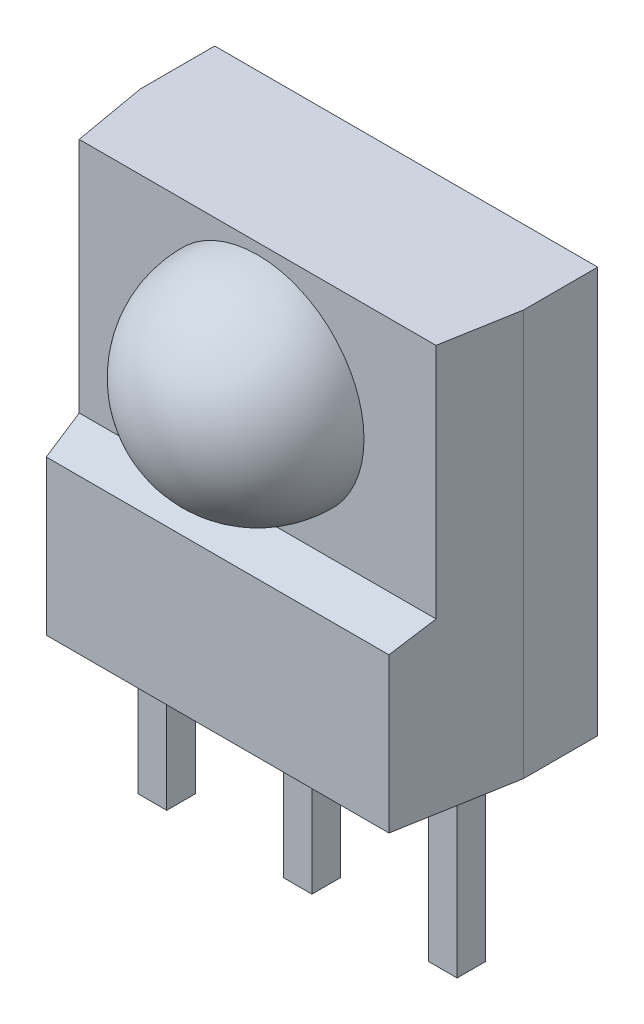
SolidWorks part; units mm, degrees
ref_plane "Plano frontal" through (0, 0, 0) normal (0, 0, 1) x (1, 0, 0)
ref_plane "Plano superior" through (0, 0, 0) normal (0, 1, 0) x (1, 0, 0)
ref_plane "Plano direito" through (0, 0, 0) normal (1, 0, 0) x (0, 0, -1)
sketch "Esboço1" plane through (0, 0, 0) normal (0, 1, 0) x (1, 0, 0)
  line L1 (-3.35, -1.65) -> (3.35, -1.65)
  line L2 (-3.35, -1.65) -> (-3.35, 1.65)
  line L3 (-3.35, 1.65) -> (3.35, 1.65)
  line L4 (3.35, -1.65) -> (3.35, 1.65)
  line L5 (-3.35, -1.65) -> (3.35, 1.65) construction
  line L6 (-3.35, 1.65) -> (3.35, -1.65) construction
  point P0 (0, 0)
  dimension "D1" = 6.7
  dimension "D2" = 3.3
extrude "Ressalto-extrusão1" add sketch "Esboço1" along normal blind 7.1
sketch "Esboço2" plane through (0, 0, 1.65) normal (0, 0, 1) x (1, 0, 0)
  line L0 (3.35, 7.1) -> (3.35, 0) construction
  line L1 (-3.35, 7.1) -> (3.35, 7.1)
  line L2 (-3.35, 7.1) -> (-3.35, 3)
  line L3 (-3.35, 3) -> (3.35, 3)
  line L4 (3.35, 7.1) -> (3.35, 3)
  line L5 (-3.35, 0) -> (3.35, 0) construction
  dimension "D1" = 3
extrude "Corte-extrusão1" cut sketch "Esboço2" against normal blind 0.7
sketch "Esboço3" plane through (0, 0, 0.95) normal (0, 0, 1) x (1, 0, 0)
  line L0 (0, 7.1) -> (0, 3) construction
  line L1 (3.35, 7.1) -> (-3.35, 7.1) construction
  line L2 (-3.35, 3) -> (3.35, 3) construction
  line L3 (0, 6.911) -> (0, 3.189)
  arc A0 (0, 3.189) -> (0, 6.911) centre (0, 5.05) ccw
revolve "Revolução1" add sketch "Esboço3" angle 180 about L0
sketch "Esboço4" plane through (0, 0, 0) normal (0, -1, 0) x (1, 0, 0)
  line L0 (-3.35, 0) -> (3.35, 0) construction
  line L1 (-3.35, -1.65) -> (-3.35, 1.65) construction
  line L2 (3.35, 1.65) -> (3.35, -1.65) construction
  line L3 (-0.25, -0.25) -> (0.25, -0.25)
  line L4 (-2.79, -0.25) -> (-2.29, -0.25)
  line L5 (-2.79, -0.25) -> (-2.79, 0.25)
  line L6 (-2.79, 0.25) -> (-2.29, 0.25)
  line L7 (-2.29, -0.25) -> (-2.29, 0.25)
  line L8 (-2.79, -0.25) -> (-2.29, 0.25) construction
  line L9 (-2.79, 0.25) -> (-2.29, -0.25) construction
  line L10 (-0.25, -0.25) -> (-0.25, 0.25)
  line L11 (-0.25, 0.25) -> (0.25, 0.25)
  line L12 (0.25, -0.25) -> (0.25, 0.25)
  line L13 (-0.25, -0.25) -> (0.25, 0.25) construction
  line L14 (-0.25, 0.25) -> (0.25, -0.25) construction
  line L15 (2.29, -0.25) -> (2.79, -0.25)
  line L16 (2.29, -0.25) -> (2.29, 0.25)
  line L17 (2.29, 0.25) -> (2.79, 0.25)
  line L18 (2.79, -0.25) -> (2.79, 0.25)
  line L19 (2.29, -0.25) -> (2.79, 0.25) construction
  line L20 (2.29, 0.25) -> (2.79, -0.25) construction
  point P6 (-2.54, 0)
  point P13 (0, 0)
  point P18 (2.54, 0)
  dimension "D1" = 0.5
  dimension "D2" = 0.5
  dimension "D4" = 2.54
  dimension "D3" = 3
extrude "Ressalto-extrusão2" add sketch "Esboço4" along normal blind 3
chamfer "Chanfro1" distance 0.3 angle 70 1 edges at (0, 3, 1.65) first distance on face at (0, 1.5, 1.65)
chamfer "Chanfro2" distance 2 angle 10 2 edges at (3.35, 1.35, 1.65) (-3.35, 1.35, 1.65) first distance on face at (3.35, 3.3091, 0.3167) first distance on face at (-3.35, 3.3091, 0.3167)
